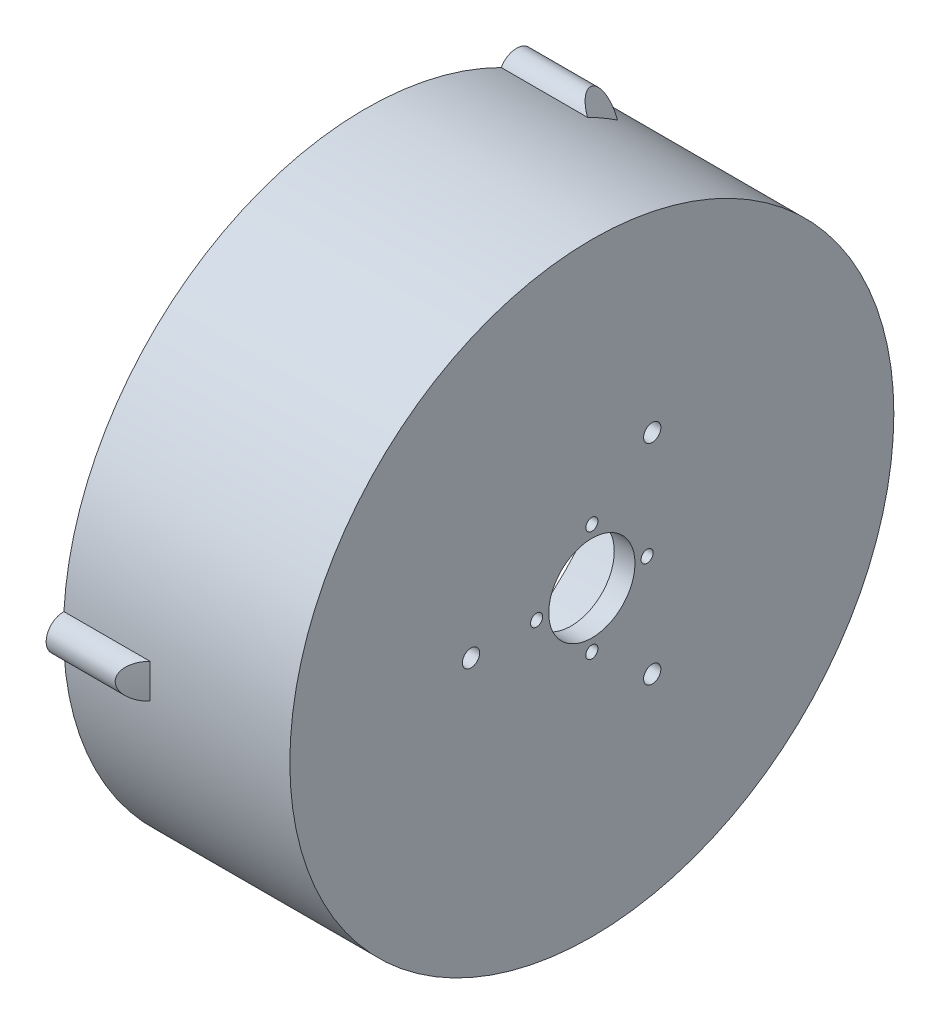
SolidWorks part; units mm, degrees
ref_plane "Front Plane" through (0, 0, 0) normal (1, 0, 0) x (0, 1, 0)
ref_plane "Top Plane" through (0, 0, 0) normal (0, 0, 1) x (0, 1, 0)
ref_plane "Right Plane" through (0, 0, 0) normal (0, 1, 0) x (-1, 0, 0)
sketch "Sketch1" plane through (0, 0, 0) normal (0, 1, 0) x (-1, 0, 0)
  line L0 (0, 0) -> (0, 87.5)
  line L4 (65.6, 87.5) -> (65.6, 81.5)
  line L6 (6, 81.5) -> (6, 0)
  line L9 (-38.1109, 0) -> (43.1075, 0) construction
  line L10 (6, 0) -> (0, 0)
  line L11 (65.6, 87.5) -> (0, 87.5)
  line L13 (65.6, 81.5) -> (6, 81.5)
  dimension "D1" = 6
  dimension "D2" = 6
  dimension "D3" = 87.5
  dimension "D4" = 65.6
revolve "Revolve1" add sketch "Sketch1" angle 360 about L9
sketch "Sketch3" plane through (0, 0, 0) normal (1, 0, 0) x (0, 1, 0)
  circle A0 centre (0, 0) radius 12.5
  dimension "D1" = 25
extrude "Cut-Extrude2" cut sketch "Sketch3" against normal blind 30
sketch "Sketch4" plane through (-65.6, 0, 0) normal (-1, 0, 0) x (0, -1, 0)
  line L0 (0, 0) -> (0, 87.5) construction
  line L1 (0, 0) -> (-75.7772, -43.75) construction
  line L2 (0, 0) -> (75.7772, -43.75) construction
  circle A0 centre (0, 87.5) radius 5
  circle A1 centre (-75.7772, -43.75) radius 5
  circle A2 centre (75.7772, -43.75) radius 5
  circle A3 centre (0, 0) radius 87.5 construction
  point P8 (0, 87.5)
  dimension "D3" = 10
  dimension "D1" = 120
  dimension "D2" = 120
extrude "Boss-Extrude1" add sketch "Sketch4" against normal blind 15
sketch "Sketch5" plane through (-65.6, 0, 0) normal (-1, 0, 0) x (0, -1, 0)
  circle A0 centre (0, 87.5) radius 2.5
  dimension "D1" = 5
extrude "Cut-Extrude3" cut sketch "Sketch5" against normal blind 10.5
pattern_circular "CirPattern1" count 3 every 120 about axis through (-6, 0, 0) along (1, 0, 0) of "Cut-Extrude3"
chamfer "Chamfer1" distance 10 angle 45 1 edges at (-50.6, 75.7772, -43.75)
chamfer "Chamfer2" distance 10 angle 45 1 edges at (-50.6, 0, 87.5)
chamfer "Chamfer3" distance 10 angle 45 1 edges at (-50.6, -75.7772, -43.75)
sketch "Sketch6" plane through (0, 0, 0) normal (1, 0, 0) x (0, 1, 0)
  line L0 (-14.25, 0) -> (14.25, 0) construction
  line L1 (0, 14.25) -> (0, -14.25) construction
  circle A0 centre (-16, 0) radius 1.75
  circle A1 centre (16, 0) radius 1.75
  circle A2 centre (0, 16) radius 1.75
  circle A3 centre (0, -16) radius 1.75
  dimension "D1" = 3.5
  dimension "D3" = 3.5
  dimension "D4" = 3.5
  dimension "D2" = 28.5
  dimension "D5" = 28.5
extrude "Cut-Extrude4" cut sketch "Sketch6" against normal blind 10.5
sketch "Sketch7" plane through (0, 0, 0) normal (1, 0, 0) x (0, 1, 0)
  circle A0 centre (0, 35) radius 2.5
  dimension "D1" = 5
  dimension "D2" = 35
extrude "Cut-Extrude5" cut sketch "Sketch7" against normal blind 10.5
pattern_circular "CirPattern2" count 3 every 120 about axis through (-6, 0, 0) along (1, 0, 0) of "Cut-Extrude5"
